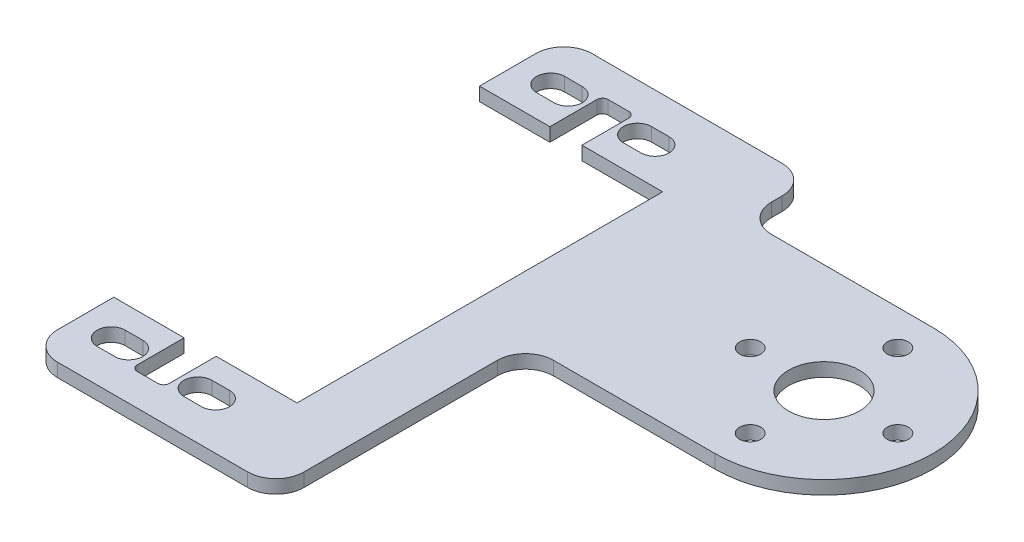
SolidWorks part; units mm, degrees
material "5052-H32"
ref_plane "Front Plane" through (0, 0, 0) normal (0, 0, 1) x (1, 0, 0)
ref_plane "Top Plane" through (0, 0, 0) normal (0, 1, 0) x (1, 0, 0)
ref_plane "Right Plane" through (0, 0, 0) normal (1, 0, 0) x (0, 0, -1)
sketch "Sketch1" plane through (0, 0, 0) normal (0, 1, 0) x (1, 0, 0)
  line L0 (0, 8.3312) -> (0, -8.3312) construction
  line L1 (-8.3312, 0) -> (8.3312, 0) construction
  line L2 (8.3312, 0) -> (12.3063, 0) construction
  line L3 (0, 8.3312) -> (0, 12.3063) construction
  line L4 (0, -8.3312) -> (0, -12.3063) construction
  line L5 (12.3063, 12.3063) -> (12.3063, -12.3063)
  line L6 (-21.3995, 12.3063) -> (12.3063, 12.3063)
  line L7 (-21.3995, -12.3063) -> (12.3063, -12.3063)
  line L8 (-21.3995, 12.3063) -> (-21.3995, 19.8501)
  line L9 (-21.3995, 19.8501) -> (-49.2125, 19.8501)
  line L10 (-49.2125, 19.8501) -> (-49.2125, -40.4749)
  line L11 (-49.2125, -40.4749) -> (-21.3995, -40.4749)
  line L12 (-21.3995, -40.4749) -> (-21.3995, -12.3063)
  circle A0 centre (0, 0) radius 4.0005
  circle A1 centre (0, 8.3312) radius 1.1938
  circle A2 centre (8.3312, 0) radius 1.1938
  circle A3 centre (0, -8.3312) radius 1.1938
  circle A4 centre (-8.3312, 0) radius 1.1938
  dimension "D2" = 2.3876
  dimension "D3" = 8.001
  dimension "D1" = 16.6624
  dimension "D4" = 24.6126
  dimension "D5" = 12.3063
  dimension "D6" = 33.7058
  dimension "D7" = 60.325
  dimension "D8" = 28.1686
  dimension "D9" = 27.813
sheet metal parameters "Sheet-Metal1" thickness 1.524 parameters "D1"=0.8128
base flange "Base-Flange1" sketch "Sketch1" thickness 1.524 reverse thickness direction yes parameters "D1"=0.8128
sketch "Sketch3" plane through (0, 1.524, 0) normal (0, 1, 0) x (1, 0, 0)
  line L0 (-49.2125, 19.8501) -> (-49.2125, -40.4749) construction
  line L1 (-49.2125, 10.3251) -> (-28.5369, 10.3251)
  line L2 (-49.2125, 10.3251) -> (-49.2125, -30.9499)
  line L3 (-49.2125, -30.9499) -> (-28.5369, -30.9499)
  line L4 (-28.5369, 10.3251) -> (-28.5369, -30.9499)
  line L5 (-49.2125, -40.4749) -> (-21.3995, -40.4749) construction
  dimension "D1" = 9.525
  dimension "D2" = 41.275
  dimension "D3" = 20.6756
extrude "Extrude1" cut sketch "Sketch3" against normal blind 1.524
sketch "Sketch4" plane through (0, 1.524, 0) normal (0, 1, 0) x (1, 0, 0)
  line L0 (-28.5369, 10.3251) -> (-49.2125, 10.3251) construction
  line L1 (-41.275, 10.3251) -> (-37.6555, 10.3251)
  line L2 (-41.275, 10.3251) -> (-41.275, 16.2687)
  line L3 (-41.275, 16.2687) -> (-37.6555, 16.2687)
  line L4 (-37.6555, 10.3251) -> (-37.6555, 16.2687)
  line L5 (-49.2125, -30.9499) -> (-28.5369, -30.9499) construction
  line L6 (-41.275, -30.9499) -> (-37.6555, -30.9499)
  line L7 (-41.275, -30.9499) -> (-41.275, -36.8935)
  line L8 (-41.275, -36.8935) -> (-37.6555, -36.8935)
  line L9 (-37.6555, -30.9499) -> (-37.6555, -36.8935)
  line L10 (-49.2125, 19.8501) -> (-49.2125, 10.3251) construction
  line L11 (-34.5567, -35.1155) -> (-44.3611, -35.1155) construction
  line L12 (-39.4589, -35.1155) -> (-39.4589, 14.4907) construction
  line L13 (-44.3611, 14.4907) -> (-34.5567, 14.4907) construction
  line L16 (-35.5473, 14.4907) -> (-33.5661, 14.4907) construction
  line L17 (-35.5473, 16.0782) -> (-33.5661, 16.0782)
  line L18 (-35.5473, 12.9032) -> (-33.5661, 12.9032)
  line L19 (-45.3517, 14.4907) -> (-43.3705, 14.4907) construction
  line L20 (-45.3517, 16.0782) -> (-43.3705, 16.0782)
  line L21 (-45.3517, 12.9032) -> (-43.3705, 12.9032)
  line L22 (-35.5473, -35.1155) -> (-33.5661, -35.1155) construction
  line L23 (-35.5473, -33.528) -> (-33.5661, -33.528)
  line L24 (-35.5473, -36.703) -> (-33.5661, -36.703)
  line L25 (-45.3517, -35.1155) -> (-43.3705, -35.1155) construction
  line L26 (-45.3517, -33.528) -> (-43.3705, -33.528)
  line L27 (-45.3517, -36.703) -> (-43.3705, -36.703)
  line L28 (-46.9392, -35.1155) -> (-41.783, -35.1155) construction
  line L29 (-28.5369, -10.3124) -> (-39.4589, -10.3124) construction
  line L30 (-28.5369, -30.9499) -> (-28.5369, 10.3251) construction
  arc A0 (-35.5473, 16.0782) -> (-35.5473, 12.9032) centre (-35.5473, 14.4907) ccw
  arc A1 (-33.5661, 12.9032) -> (-33.5661, 16.0782) centre (-33.5661, 14.4907) ccw
  arc A2 (-45.3517, 16.0782) -> (-45.3517, 12.9032) centre (-45.3517, 14.4907) ccw
  arc A3 (-43.3705, 12.9032) -> (-43.3705, 16.0782) centre (-43.3705, 14.4907) ccw
  arc A4 (-35.5473, -33.528) -> (-35.5473, -36.703) centre (-35.5473, -35.1155) ccw
  arc A5 (-33.5661, -36.703) -> (-33.5661, -33.528) centre (-33.5661, -35.1155) ccw
  arc A6 (-45.3517, -33.528) -> (-45.3517, -36.703) centre (-45.3517, -35.1155) ccw
  arc A7 (-43.3705, -36.703) -> (-43.3705, -33.528) centre (-43.3705, -35.1155) ccw
  point P26 (-34.5567, 14.4907)
  point P32 (-44.3611, 14.4907)
  point P39 (-34.5567, -35.1155)
  point P46 (-44.3611, -35.1155)
  dimension "D1" = 7.9375
  dimension "D2" = 5.9436
  dimension "D3" = 11.557
  dimension "D4" = 49.6062
  dimension "D5" = 3.175
  dimension "D6" = 5.1562
  dimension "D7" = 9.8044
  dimension "D8" = 10.922
extrude "Extrude2" cut sketch "Sketch4" against normal blind 1.524
fillet "Fillet1" radius 3.175 6 edges at (-49.2125, 0.762, 40.4749) (-21.3995, 0.762, 40.4749) (-49.2125, 0.762, -19.8501) (-21.3995, 0.762, -19.8501) (-21.3995, 0.762, 12.3063) (-21.3995, 0.762, -12.3063)
fillet "Fillet2" 2 edges at (12.3063, 0.762, -12.3063) (12.3063, 0.762, 12.3063) type full round first side face at (-2.9591, 0.762, -12.3063) second side face at (-2.9591, 0.762, 12.3063) middle face at (12.3063, 0.762, 0)
fillet "Fillet3" radius 0.635 4 edges at (-37.6555, 0.762, 36.8935) (-41.275, 0.762, 36.8935) (-37.6555, 0.762, -16.2687) (-41.275, 0.762, -16.2687)
flat pattern "Flat-Pattern1" [suppressed]
sketch "Bend-Lines1" plane through (0, 0, 0) normal (0, 1, 0) x (-1, 0, 0)
